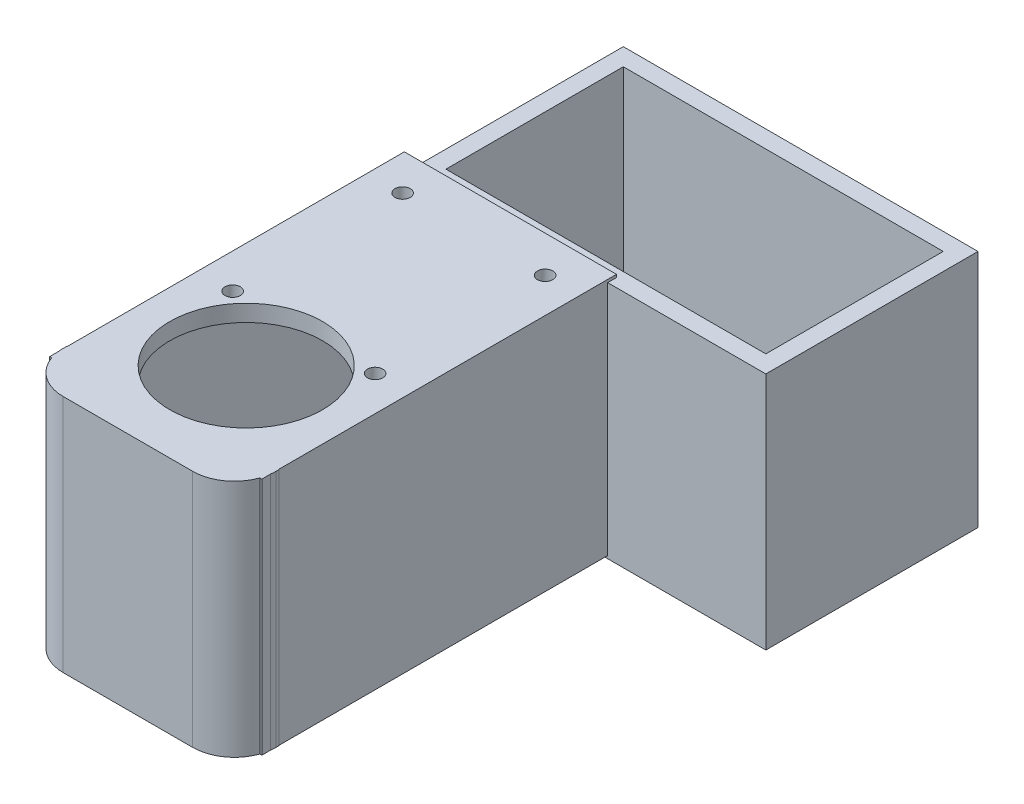
SolidWorks part; units mm, degrees
ref_plane "Front Plane" through (0, 0, 0) normal (0, 0, 1) x (1, 0, 0)
ref_plane "Top Plane" through (0, 0, 0) normal (0, 1, 0) x (1, 0, 0)
ref_plane "Right Plane" through (0, 0, 0) normal (1, 0, 0) x (0, 0, -1)
ref_plane "PZ_m38_010" through (0, 0, -38.01) normal (0, 0, 1) x (1, 0, 0)
sketch "S_box1" plane through (0, 0, -38.01) normal (0, 0, 1) x (1, 0, 0)
  line L0 (-15.26, 2.625) -> (15.26, 2.625)
  line L1 (15.26, 2.625) -> (15.26, 37.025)
  line L2 (15.26, 37.025) -> (-15.26, 37.025)
  line L3 (-15.26, 37.025) -> (-15.26, 2.625)
  dimension "P1" = 15.26
  dimension "P2" = 2.625
  dimension "P3" = 15.26
  dimension "P4" = 2.625
  dimension "P5" = 15.26
  dimension "P6" = 37.025
  dimension "P7" = 15.26
  dimension "P8" = 37.025
extrude "Boss_1" add sketch "S_box1" along normal blind 2.5
ref_plane "PZ_p10_510" through (0, 0, 10.51) normal (0, 0, 1) x (1, 0, 0)
sketch "S_box2" plane through (0, 0, 10.51) normal (0, 0, 1) x (1, 0, 0)
  line L0 (-15.26, 2.625) -> (15.26, 2.625)
  line L1 (15.26, 2.625) -> (15.26, 37.025)
  line L2 (15.26, 37.025) -> (-15.26, 37.025)
  line L3 (-15.26, 37.025) -> (-15.26, 2.625)
  dimension "P1" = 15.26
  dimension "P2" = 2.625
  dimension "P3" = 15.26
  dimension "P4" = 2.625
  dimension "P5" = 15.26
  dimension "P6" = 37.025
  dimension "P7" = 15.26
  dimension "P8" = 37.025
extrude "Boss_2" add sketch "S_box2" along normal blind 2.5
sketch "S_box3" plane through (0, 0, -38.01) normal (0, 0, 1) x (1, 0, 0)
  line L0 (-15.26, 2.625) -> (-12.76, 2.625)
  line L1 (-12.76, 2.625) -> (-12.76, 37.025)
  line L2 (-12.76, 37.025) -> (-15.26, 37.025)
  line L3 (-15.26, 37.025) -> (-15.26, 2.625)
  dimension "P1" = 15.26
  dimension "P2" = 2.625
  dimension "P3" = 12.76
  dimension "P4" = 2.625
  dimension "P5" = 12.76
  dimension "P6" = 37.025
  dimension "P7" = 15.26
  dimension "P8" = 37.025
extrude "Boss_3" add sketch "S_box3" along normal blind 51.02
sketch "S_box4" plane through (0, 0, -38.01) normal (0, 0, 1) x (1, 0, 0)
  line L0 (12.76, 2.625) -> (15.26, 2.625)
  line L1 (15.26, 2.625) -> (15.26, 37.025)
  line L2 (15.26, 37.025) -> (12.76, 37.025)
  line L3 (12.76, 37.025) -> (12.76, 2.625)
  dimension "P1" = 12.76
  dimension "P2" = 2.625
  dimension "P3" = 15.26
  dimension "P4" = 2.625
  dimension "P5" = 15.26
  dimension "P6" = 37.025
  dimension "P7" = 12.76
  dimension "P8" = 37.025
extrude "Boss_4" add sketch "S_box4" along normal blind 51.02
sketch "S_box5" plane through (0, 0, -38.01) normal (0, 0, 1) x (1, 0, 0)
  line L0 (-15.26, 34.625) -> (15.26, 34.625)
  line L1 (15.26, 34.625) -> (15.26, 37.025)
  line L2 (15.26, 37.025) -> (-15.26, 37.025)
  line L3 (-15.26, 37.025) -> (-15.26, 34.625)
  dimension "P1" = 15.26
  dimension "P2" = 34.625
  dimension "P3" = 15.26
  dimension "P4" = 34.625
  dimension "P5" = 15.26
  dimension "P6" = 37.025
  dimension "P7" = 15.26
  dimension "P8" = 37.025
extrude "Boss_5" add sketch "S_box5" along normal blind 51.02
ref_plane "PZ_m67_260" through (0, 0, -67.26) normal (0, 0, 1) x (1, 0, 0)
sketch "S_box6" plane through (0, 0, -67.26) normal (0, 0, 1) x (1, 0, 0)
  line L0 (-13.01, 2.225) -> (-10.51, 2.225)
  line L1 (-10.51, 2.225) -> (-10.51, 36.625)
  line L2 (-10.51, 36.625) -> (-13.01, 36.625)
  line L3 (-13.01, 36.625) -> (-13.01, 2.225)
  dimension "P1" = 13.01
  dimension "P2" = 2.225
  dimension "P3" = 10.51
  dimension "P4" = 2.225
  dimension "P5" = 10.51
  dimension "P6" = 36.625
  dimension "P7" = 13.01
  dimension "P8" = 36.625
extrude "Boss_6" add sketch "S_box6" along normal blind 30.52
sketch "S_box7" plane through (0, 0, -67.26) normal (0, 0, 1) x (1, 0, 0)
  line L0 (35.51, 2.225) -> (38.01, 2.225)
  line L1 (38.01, 2.225) -> (38.01, 36.625)
  line L2 (38.01, 36.625) -> (35.51, 36.625)
  line L3 (35.51, 36.625) -> (35.51, 2.225)
  dimension "P1" = 35.51
  dimension "P2" = 2.225
  dimension "P3" = 38.01
  dimension "P4" = 2.225
  dimension "P5" = 38.01
  dimension "P6" = 36.625
  dimension "P7" = 35.51
  dimension "P8" = 36.625
extrude "Boss_7" add sketch "S_box7" along normal blind 30.52
sketch "S_box8" plane through (0, 0, -67.26) normal (0, 0, 1) x (1, 0, 0)
  line L0 (-13.01, 2.225) -> (38.01, 2.225)
  line L1 (38.01, 2.225) -> (38.01, 36.625)
  line L2 (38.01, 36.625) -> (-13.01, 36.625)
  line L3 (-13.01, 36.625) -> (-13.01, 2.225)
  dimension "P1" = 13.01
  dimension "P2" = 2.225
  dimension "P3" = 38.01
  dimension "P4" = 2.225
  dimension "P5" = 38.01
  dimension "P6" = 36.625
  dimension "P7" = 13.01
  dimension "P8" = 36.625
extrude "Boss_8" add sketch "S_box8" along normal blind 2.5
ref_plane "PZ_m39_240" through (0, 0, -39.24) normal (0, 0, 1) x (1, 0, 0)
sketch "S_box9" plane through (0, 0, -39.24) normal (0, 0, 1) x (1, 0, 0)
  line L0 (-13.01, 2.225) -> (38.01, 2.225)
  line L1 (38.01, 2.225) -> (38.01, 36.625)
  line L2 (38.01, 36.625) -> (-13.01, 36.625)
  line L3 (-13.01, 36.625) -> (-13.01, 2.225)
  dimension "P1" = 13.01
  dimension "P2" = 2.225
  dimension "P3" = 38.01
  dimension "P4" = 2.225
  dimension "P5" = 38.01
  dimension "P6" = 36.625
  dimension "P7" = 13.01
  dimension "P8" = 36.625
extrude "Boss_9" add sketch "S_box9" along normal blind 2.5
sketch "S_box10" plane through (0, 0, -67.26) normal (0, 0, 1) x (1, 0, 0)
  line L0 (-13.01, 2.225) -> (38.01, 2.225)
  line L1 (38.01, 2.225) -> (38.01, 4.625)
  line L2 (38.01, 4.625) -> (-13.01, 4.625)
  line L3 (-13.01, 4.625) -> (-13.01, 2.225)
  dimension "P1" = 13.01
  dimension "P2" = 2.225
  dimension "P3" = 38.01
  dimension "P4" = 2.225
  dimension "P5" = 38.01
  dimension "P6" = 4.625
  dimension "P7" = 13.01
  dimension "P8" = 4.625
extrude "Boss_10" add sketch "S_box10" along normal blind 30.52
ref_plane "PY_p2_625" through (0, 2.625, 0) normal (0, 1, 0) x (1, 0, 0)
sketch "S_prism11" plane through (0, 2.625, 0) normal (0, 1, 0) x (1, 0, 0)
  line L0 (-15.31, -10.56) -> (15.31, -10.56)
  line L1 (15.31, -10.56) -> (15.31, -11.01)
  line L2 (9.31, -17.01) -> (-9.31, -17.01)
  line L3 (-15.31, -11.01) -> (-15.31, -10.56)
  arc A0 (15.31, -11.01) -> (9.31, -17.01) centre (9.3099, -11.0099) cw
  arc A1 (-9.31, -17.01) -> (-15.31, -11.01) centre (-9.3099, -11.0099) cw
extrude "Boss_11" add sketch "S_prism11" along normal blind 34.4
ref_plane "PY_p34_525" through (0, 34.525, 0) normal (0, 1, 0) x (1, 0, 0)
sketch "S_hole12" plane through (0, 34.525, 0) normal (0, 1, 0) x (1, 0, 0)
  circle A0 centre (0, 0) radius 11
  dimension "D1_S_hole12" = 22
extrude "Hole_12" cut sketch "S_hole12" along normal blind 2.6
sketch "S_hole13" plane through (0, 34.525, 0) normal (0, 1, 0) x (1, 0, 0)
  circle A0 centre (-10.25, 8.3) radius 1.1
  dimension "D1_S_hole13" = 2.2
  dimension "P2" = 10.25
  dimension "P3" = 8.3
extrude "Hole_13" cut sketch "S_hole13" along normal blind 2.6
sketch "S_hole14" plane through (0, 34.525, 0) normal (0, 1, 0) x (1, 0, 0)
  circle A0 centre (10.25, 8.3) radius 1.1
  dimension "D1_S_hole14" = 2.2
  dimension "P2" = 10.25
  dimension "P3" = 8.3
extrude "Hole_14" cut sketch "S_hole14" along normal blind 2.6
sketch "S_hole15" plane through (0, 34.525, 0) normal (0, 1, 0) x (1, 0, 0)
  circle A0 centre (-10.25, 32.75) radius 1.1
  dimension "D1_S_hole15" = 2.2
  dimension "P2" = 10.25
  dimension "P3" = 32.75
extrude "Hole_15" cut sketch "S_hole15" along normal blind 2.6
sketch "S_hole16" plane through (0, 34.525, 0) normal (0, 1, 0) x (1, 0, 0)
  circle A0 centre (10.25, 32.75) radius 1.1
  dimension "D1_S_hole16" = 2.2
  dimension "P2" = 10.25
  dimension "P3" = 32.75
extrude "Hole_16" cut sketch "S_hole16" along normal blind 2.6
ref_plane "PY_p2_125" through (0, 2.125, 0) normal (0, 1, 0) x (1, 0, 0)
sketch "S_hole17" plane through (0, 2.125, 0) normal (0, 1, 0) x (1, 0, 0)
  circle A0 centre (0, 52) radius 11
  dimension "D1_S_hole17" = 22
  dimension "P2" = 52
extrude "Hole_17" cut sketch "S_hole17" along normal blind 2.6
sketch "S_hole18" plane through (0, 2.125, 0) normal (0, 1, 0) x (1, 0, 0)
  circle A0 centre (8.3, 62.25) radius 1.1
  dimension "D1_S_hole18" = 2.2
  dimension "P2" = 8.3
  dimension "P3" = 62.25
extrude "Hole_18" cut sketch "S_hole18" along normal blind 2.6
sketch "S_hole19" plane through (0, 2.125, 0) normal (0, 1, 0) x (1, 0, 0)
  circle A0 centre (8.3, 41.75) radius 1.1
  dimension "D1_S_hole19" = 2.2
  dimension "P2" = 8.3
  dimension "P3" = 41.75
extrude "Hole_19" cut sketch "S_hole19" along normal blind 2.6
sketch "S_hole20" plane through (0, 2.125, 0) normal (0, 1, 0) x (1, 0, 0)
  circle A0 centre (32.75, 62.25) radius 1.1
  dimension "D1_S_hole20" = 2.2
  dimension "P2" = 32.75
  dimension "P3" = 62.25
extrude "Hole_20" cut sketch "S_hole20" along normal blind 2.6
sketch "S_hole21" plane through (0, 2.125, 0) normal (0, 1, 0) x (1, 0, 0)
  circle A0 centre (32.75, 41.75) radius 1.1
  dimension "D1_S_hole21" = 2.2
  dimension "P2" = 32.75
  dimension "P3" = 41.75
extrude "Hole_21" cut sketch "S_hole21" along normal blind 2.6
equation "\"plate_t\" = 3"
equation "\"clearance\" = 0.4"
